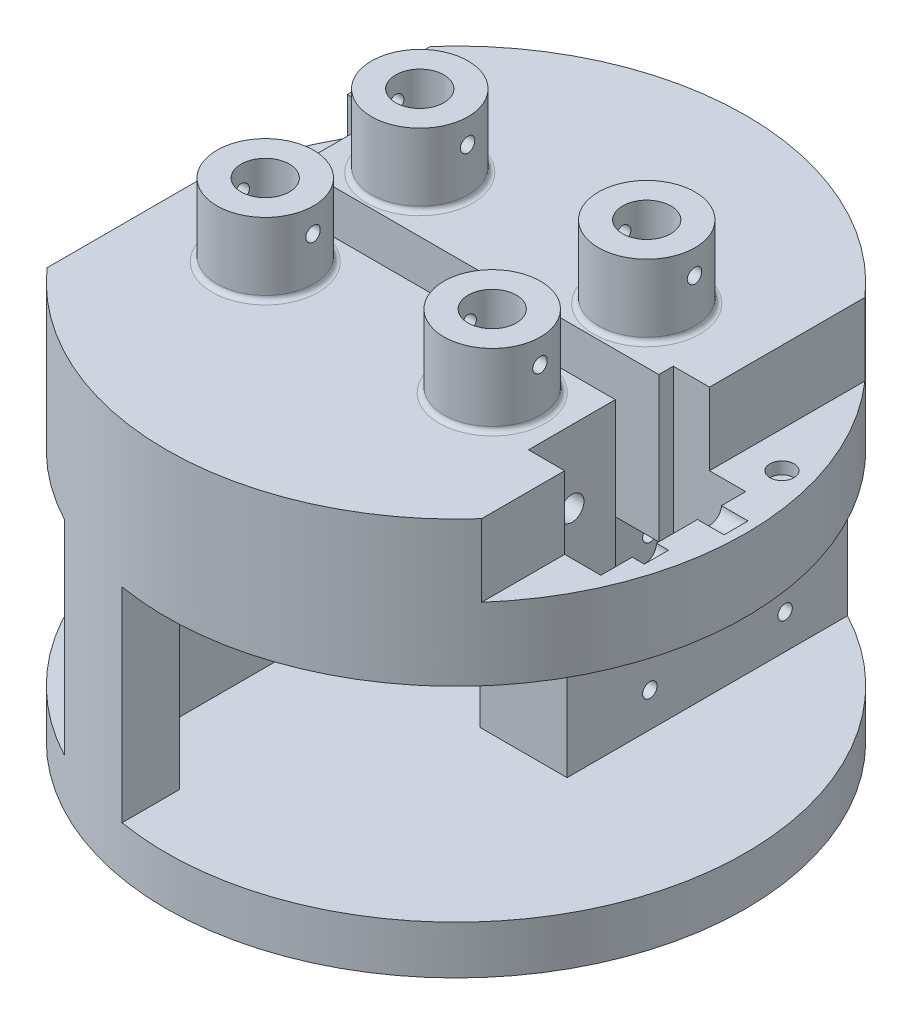
SolidWorks part; units mm, degrees
ref_plane "Front Plane" through (0, 0, 0) normal (0, 0, 1) x (1, 0, 0)
ref_plane "Top Plane" through (0, 0, 0) normal (0, 1, 0) x (1, 0, 0)
ref_plane "Right Plane" through (0, 0, 0) normal (1, 0, 0) x (0, 0, -1)
sketch "Sketch1" plane through (0, 0, 0) normal (0, 1, 0) x (1, 0, 0)
  circle A0 centre (0, 0) radius 60
  dimension "D1" = 120
extrude "Boss-Extrude1" add sketch "Sketch1" along normal blind 10
sketch "Sketch5" plane through (0, 10, 0) normal (0, 1, 0) x (1, 0, 0)
  line L0 (-73.7107, 0) -> (83.6973, 0) construction
  line L1 (0, -69.1137) -> (0, 62.4559) construction
  line L2 (0, 0) -> (20, 0) construction
  line L3 (0, 0) -> (-20, 0) construction
  line L4 (15, -47.3) -> (15, -5)
  line L5 (-15, 47.3) -> (23, 47.3)
  line L6 (-15, 47.3) -> (-15, 5)
  line L7 (-15, 5) -> (23, 5)
  line L8 (23, 47.3) -> (23, 5)
  line L9 (-15, 47.3) -> (23, 5) construction
  line L10 (-15, 5) -> (23, 47.3) construction
  line L11 (15, -47.3) -> (-23, -47.3)
  line L12 (-23, -47.3) -> (-23, -5)
  line L13 (15, -5) -> (-23, -5)
  line L15 (10, 0) -> (28, 0)
  line L16 (28, 53.066) -> (28, 0)
  line L20 (-28, -53.066) -> (-28, 0)
  line L22 (10, 59.1608) -> (10, 47.3)
  line L24 (10, 5) -> (10, 0)
  line L26 (-10, 0) -> (-10, -5)
  line L27 (-10, -47.3) -> (-10, -59.1608)
  line L28 (-10, 0) -> (-28, 0)
  line L29 (-20, 52.3) -> (28, 52.3) construction
  line L30 (-20, 52.3) -> (-20, 0) construction
  line L31 (28, 52.3) -> (28, 0) construction
  line L32 (20, -52.3) -> (20, 0) construction
  line L33 (20, -52.3) -> (-28, -52.3) construction
  line L34 (-28, -52.3) -> (-28, 0) construction
  line L35 (-20, 0) -> (28, 0) construction
  line L37 (20, 0) -> (-28, 0) construction
  line L38 (-10, 0) -> (5, 0)
  line L39 (-10, 0) -> (-10, -5)
  line L40 (-10, -5) -> (5, -5)
  line L41 (5, 0) -> (5, -5)
  line L42 (-5, 5) -> (10, 5)
  line L43 (-5, 5) -> (-5, 0)
  line L44 (-5, 0) -> (10, 0)
  line L45 (10, 5) -> (10, 0)
  circle A0 centre (0, 0) radius 60
  point P7 (4, 26.15)
  point P19 (0, 0)
  dimension "D10" = 120
  dimension "D1" = 20
  dimension "D2" = 20
  dimension "D4" = 42.3
  dimension "D5" = 5
  dimension "D6" = 5
  dimension "D7" = 38
  dimension "D11" = 20
  dimension "D12" = 10
  dimension "D9" = 10
  dimension "D13" = 5
  dimension "D8" = 5
  dimension "D3" = 2
extrude "Boss-Extrude5" add sketch "Sketch5" along normal blind 42.3 contours L7 L24 L15 L16 L22 L5 L8 | L27 L11 L12 L13 L26 L15 L20 A0 region at (-10.6184, 10, 53.2304) region at (10.6184, 10, -2.5)
sketch "Sketch6" plane through (28, 0, 0) normal (1, 0, 0) x (0, 0, -1)
  line L6 (26.15, 52.3) -> (26.15, 10) construction
  line L11 (5, 31.15) -> (47.3, 31.15) construction
  line L18 (12.15, 45.15) -> (40.15, 45.15) construction
  line L20 (5, 10) -> (47.3, 10)
  line L21 (5, 52.3) -> (5, 10)
  line L22 (47.3, 52.3) -> (5, 52.3)
  line L23 (47.3, 10) -> (47.3, 52.3)
  line L24 (5, 10) -> (47.3, 10)
  line L25 (5, 52.3) -> (5, 10)
  line L26 (47.3, 52.3) -> (5, 52.3)
  line L27 (47.3, 10) -> (47.3, 52.3)
  line L28 (12.15, 45.15) -> (12.15, 17.15) construction
  line L29 (12.15, 17.15) -> (40.15, 17.15) construction
  line L30 (40.15, 45.15) -> (40.15, 17.15) construction
  line L31 (12.15, 45.15) -> (40.15, 17.15) construction
  line L32 (12.15, 17.15) -> (40.15, 45.15) construction
  circle A4 centre (12.15, 45.15) radius 1.5
  circle A5 centre (40.15, 45.15) radius 1.5
  circle A6 centre (40.15, 17.15) radius 1.5
  circle A7 centre (12.15, 17.15) radius 1.5
  point P10 (26.15, 31.15)
  dimension "D1" = 0
  dimension "D2" = 3
  dimension "D3" = 28
  dimension "D4" = 28
extrude "Cut-Extrude1" cut sketch "Sketch6" against normal through all contours A4 | A7 | A6 | A5
pattern_circular "CirPattern1" count 2 over 360 about axis through (0, 10, 0) along (0, 1, 0) of "Cut-Extrude1"
sketch "Sketch8" plane through (0, 10, 0) normal (0, 1, 0) x (1, 0, 0)
  line L0 (10, 47.3) -> (23, 47.3) construction
  line L1 (23, 5) -> (-15, 5)
  line L2 (23, 5) -> (23, 47.3)
  line L3 (23, 47.3) -> (-15, 47.3)
  line L4 (-15, 5) -> (-15, 47.3)
  line L5 (-10, -47.3) -> (-23, -47.3) construction
  line L6 (-23, -5) -> (15, -5)
  line L7 (-23, -5) -> (-23, -47.3)
  line L8 (-23, -47.3) -> (15, -47.3)
  line L9 (15, -5) -> (15, -47.3)
  line L10 (-15, 26.15) -> (-39, 26.15) construction
  line L11 (15, -26.15) -> (39, -26.15) construction
  dimension "D1" = 38
  dimension "D2" = 38
  dimension "D3" = 24
  dimension "D4" = 24
sketch "Sketch3" plane through (0, 52.3, 0) normal (0, 1, 0) x (1, 0, 0)
  circle A11 centre (0, 0) radius 60
  dimension "D1" = 120
extrude "Boss-Extrude4" add sketch "Sketch3" along normal blind 30
sketch "Sketch4" plane through (0, 82.3, 0) normal (0, 1, 0) x (1, 0, 0)
  line L1 (-23.5, 16) -> (23.5, 16) construction
  line L2 (-23.5, 16) -> (-23.5, -16) construction
  line L3 (-23.5, -16) -> (23.5, -16) construction
  line L4 (23.5, 16) -> (23.5, -16) construction
  line L5 (-23.5, 16) -> (23.5, -16) construction
  line L6 (-23.5, -16) -> (23.5, 16) construction
  circle A0 centre (-23.5, 16) radius 5
  circle A1 centre (23.5, 16) radius 5
  circle A2 centre (23.5, -16) radius 5
  circle A3 centre (-23.5, -16) radius 5
  circle A4 centre (-23.5, 16) radius 10
  circle A5 centre (23.5, 16) radius 10
  circle A6 centre (23.5, -16) radius 10
  circle A7 centre (-23.5, -16) radius 10
  point P0 (0, 0)
  dimension "D3" = 10
  dimension "D1" = 47
  dimension "D2" = 32
  dimension "D4" = 5
extrude "Boss-Extrude6" add sketch "Sketch4" along normal blind 15
fillet "Fillet1" radius 1 4 edges at (23.5, 82.3, -6) (-23.5, 82.3, -6) (23.5, 82.3, 26) (-23.5, 82.3, 26)
sketch "Sketch7" plane through (0, 0, 0) normal (1, 0, 0) x (0, 0, -1)
  line L0 (0, 0) -> (0, 82.3) construction
  line L1 (60, 82.3) -> (-60, 82.3) construction
  line L2 (0, 82.3) -> (0, 92.3) construction
  line L3 (0, 92.3) -> (16, 92.3) construction
  line L4 (0, 92.3) -> (-16, 92.3) construction
  circle A0 centre (16, 92.3) radius 1.5
  circle A1 centre (-16, 92.3) radius 1.5
  dimension "Set screw OD" = 3
  dimension "D1" = 10
  dimension "D2" = 16
extrude "Cut-Extrude2" cut sketch "Sketch7" along normal through all both and the other way through all
sketch "Sketch9" plane through (0, 82.3, 0) normal (0, 1, 0) x (1, 0, 0)
  line L0 (-60, 0) -> (60, 0) construction
  line L1 (0, 60) -> (0, -60) construction
  line L3 (-45, 4.5) -> (45, 4.5)
  line L4 (-45, 4.5) -> (-45, -4.5)
  line L5 (-45, -4.5) -> (45, -4.5)
  line L6 (45, 4.5) -> (45, -4.5)
  line L7 (-45, 4.5) -> (45, -4.5) construction
  line L8 (-45, -4.5) -> (45, 4.5) construction
  line L9 (-52.5, 7.5) -> (-37.5, 7.5)
  line L10 (-52.5, 7.5) -> (-52.5, -7.5)
  line L11 (-52.5, -7.5) -> (-37.5, -7.5)
  line L12 (-37.5, 7.5) -> (-37.5, -7.5)
  line L13 (-52.5, 7.5) -> (-37.5, -7.5) construction
  line L14 (-52.5, -7.5) -> (-37.5, 7.5) construction
  line L15 (37.5, 7.5) -> (52.5, 7.5)
  line L16 (37.5, 7.5) -> (37.5, -7.5)
  line L17 (37.5, -7.5) -> (52.5, -7.5)
  line L18 (52.5, 7.5) -> (52.5, -7.5)
  line L19 (37.5, 7.5) -> (52.5, -7.5) construction
  line L20 (37.5, -7.5) -> (52.5, 7.5) construction
  circle A0 centre (0, 0) radius 60 construction
  point P8 (0, 0)
  point P13 (-45, 0)
  point P18 (45, 0)
  dimension "D1" = 90
  dimension "D2" = 9
  dimension "D3" = 15
  dimension "D4" = 45
extrude "Cut-Extrude6" cut sketch "Sketch9" against normal up to surface (30 mm away) contours L12 L9 L10 L11 L5 L4 L3 | L16 L3 L12 L5 | L12 L3 L4 L5 | L3 L16 L5 L6 | L18 L15 L16 L3 L6 L5 L17 region at (-46.6071, 82.3, 0) region at (-41.25, 82.3, 0) region at (0, 82.3, 0) region at (46.6071, 82.3, 0) region at (41.25, 82.3, 0) up to face at (0, 52.3, 0)
sketch "Sketch10" plane through (10, 0, 0) normal (-1, 0, 0) x (0, 0, 1)
  line L0 (-2.25, 52.3) -> (-2.25, 31.15) construction
  line L1 (-4.5, 52.3) -> (0, 52.3) construction
  circle A0 centre (-2.25, 31.15) radius 1
  dimension "Gt2 belt ID" = 2
  dimension "D1" = 21.15
sketch "Sketch11" plane through (0, 0, 0) normal (0, 0, -1) x (-1, 0, 0)
  line L1 (10, 52.3) -> (28, 52.3)
  line L2 (10, 52.3) -> (10, 10)
  line L3 (10, 10) -> (28, 10)
  line L4 (28, 52.3) -> (28, 10)
extrude "Boss-Extrude7" add sketch "Sketch11" along normal blind 5
sketch "Sketch12" plane through (-28, 0, 0) normal (-1, 0, 0) x (0, 0, 1)
  line L0 (-5, 52.3) -> (-5, 10) construction
  line L1 (-5, 52.3) -> (-5, 10)
sketch "Sketch14" plane through (0, 0, 0) normal (0, 0, 1) x (1, 0, 0)
  line L4 (10, 10) -> (28, 10)
  line L5 (28, 10) -> (28, 52.3)
  line L6 (28, 52.3) -> (10, 52.3)
  line L7 (10, 52.3) -> (10, 10)
  line L8 (10, 10) -> (28, 10)
  line L9 (28, 10) -> (28, 52.3)
  line L10 (28, 52.3) -> (10, 52.3)
  line L11 (10, 52.3) -> (10, 10)
  dimension "D1" = 0
extrude "Boss-Extrude8" add sketch "Sketch14" along normal blind 5
sketch "Sketch16" plane through (0, 82.3, 0) normal (0, 1, 0) x (1, 0, 0)
  line L0 (-37.5, -4.5) -> (-37.5, -7.5) construction
  line L1 (-52.5, 7.5) -> (-37.5, 7.5)
  line L2 (-52.5, 7.5) -> (-52.5, -7.5)
  line L3 (-52.5, -7.5) -> (-37.5, -7.5)
  line L4 (-37.5, 7.5) -> (-37.5, -7.5)
  line L5 (-52.5, -7.5) -> (-37.5, -7.5) construction
  line L7 (37.5, 7.5) -> (52.5, 7.5)
  line L8 (37.5, 7.5) -> (37.5, -7.5)
  line L9 (37.5, -7.5) -> (52.5, -7.5)
  line L10 (52.5, 7.5) -> (52.5, -7.5)
sketch "Sketch18" plane through (0, 52.3, 0) normal (0, 1, 0) x (1, 0, 0)
  line L4 (-10, -4.5) -> (-10, 4.5)
  line L5 (-10, 4.5) -> (-28, 4.5)
  line L6 (-28, 4.5) -> (-28, -4.5)
  line L7 (-28, -4.5) -> (-10, -4.5)
  line L8 (-10, -4.5) -> (-10, 4.5)
  line L9 (-10, 4.5) -> (-28, 4.5)
  line L10 (-28, 4.5) -> (-28, -4.5)
  line L11 (-28, -4.5) -> (-10, -4.5)
  line L12 (10, 4.5) -> (10, -4.5)
  line L13 (10, -4.5) -> (28, -4.5)
  line L14 (28, -4.5) -> (28, 4.5)
  line L15 (28, 4.5) -> (10, 4.5)
  line L16 (10, 4.5) -> (10, -4.5)
  line L17 (10, -4.5) -> (28, -4.5)
  line L18 (28, -4.5) -> (28, 4.5)
  line L19 (28, 4.5) -> (10, 4.5)
  dimension "D1" = 0
  dimension "D2" = 0
extrude "Boss-Extrude9" add sketch "Sketch18" along normal blind 15
sketch "Sketch19" plane through (-28, 0, 0) normal (-1, 0, 0) x (0, 0, 1)
  circle A0 centre (0, 67.5) radius 2.5
  dimension "D2" = 5
  dimension "D1" = 67.5
extrude "Cut-Extrude7" cut sketch "Sketch19" against normal blind 5 and the other way blind 30
mirror "Mirror1" about plane through (0, 0, 0) normal (1, 0, 0) of "Cut-Extrude7"
sketch "Sketch20" plane through (0, 0, 0) normal (1, 0, 0) x (0, 0, -1)
  line L0 (0, 0) -> (-50, 0) construction
  line L1 (-60, 0) -> (60, 0) construction
  circle A0 centre (-50, 0) radius 2.5
  dimension "Bearing Ball OD" = 5
  dimension "bearing ball track radius" = 50
sketch "Sketch21" plane through (0, 0, 0) normal (0, -1, 0) x (1, 0, 0)
  circle A0 centre (0, 0) radius 50
  dimension "Bearing Ball track Diameter" = 100
sweep "Cut-Sweep1" cut profiles "Sketch20" path "Sketch21"
sketch "Sketch22" plane through (0, 82.3, 0) normal (0, 1, 0) x (1, 0, 0)
  line L0 (-37.5, 7.5) -> (-37.5, -7.5) construction
  line L1 (-52.5, 7.5) -> (-37.5, 7.5)
  line L2 (-52.5, 7.5) -> (-52.5, 22.5)
  line L3 (-52.5, 22.5) -> (-37.5, 22.5)
  line L4 (-37.5, 7.5) -> (-37.5, 22.5)
  line L5 (52.5, 7.5) -> (52.5, -7.5) construction
  line L6 (37.5, -7.5) -> (52.5, -7.5)
  line L7 (37.5, -7.5) -> (37.5, -22.5)
  line L8 (37.5, -22.5) -> (52.5, -22.5)
  line L9 (52.5, -7.5) -> (52.5, -22.5)
  dimension "D1" = 15
  dimension "D2" = 15
extrude "Cut-Extrude8" cut sketch "Sketch22" against normal up to next
sketch "Sketch24" plane through (-37.5, 0, 0) normal (-1, 0, 0) x (0, 0, 1)
  line L0 (-13.5, 82.3) -> (-13.5, 52.3) construction
  line L1 (-22.5, 67.3) -> (-4.5, 67.3) construction
  line L4 (-4.5, 52.3) -> (-4.5, 82.3)
  line L5 (-4.5, 82.3) -> (-22.5, 82.3)
  line L6 (-22.5, 82.3) -> (-22.5, 52.3)
  line L7 (-22.5, 52.3) -> (-4.5, 52.3)
  line L8 (-4.5, 52.3) -> (-4.5, 82.3) construction
  line L9 (-4.5, 82.3) -> (-22.5, 82.3) construction
  line L10 (-22.5, 82.3) -> (-22.5, 52.3) construction
  line L11 (-22.5, 52.3) -> (-4.5, 52.3) construction
  circle A0 centre (-13.5, 67.3) radius 2.5
  dimension "D2" = 5
  dimension "D1" = 0
extrude "Cut-Extrude9" cut sketch "Sketch24" along normal blind 17.5 and the other way blind 5
sketch "Sketch25" plane through (37.5, 0, 0) normal (1, 0, 0) x (0, 0, -1)
  line L0 (-13.5, 82.3) -> (-13.5, 52.3) construction
  line L1 (-22.5, 67.3) -> (-4.5, 67.3) construction
  line L4 (-22.5, 52.3) -> (-4.5, 52.3)
  line L5 (-4.5, 52.3) -> (-4.5, 82.3)
  line L6 (-4.5, 82.3) -> (-22.5, 82.3)
  line L7 (-22.5, 82.3) -> (-22.5, 52.3)
  line L8 (-22.5, 52.3) -> (-4.5, 52.3) construction
  line L9 (-4.5, 52.3) -> (-4.5, 82.3) construction
  line L10 (-4.5, 82.3) -> (-22.5, 82.3) construction
  line L11 (-22.5, 82.3) -> (-22.5, 52.3) construction
  circle A0 centre (-13.5, 67.3) radius 2.5
  dimension "D2" = 5
  dimension "D1" = 0
extrude "Cut-Extrude10" cut sketch "Sketch25" along normal blind 17.5 and the other way blind 5
sketch "Sketch26" plane through (0, 82.3, 0) normal (0, 1, 0) x (1, 0, 0)
  line L0 (45, 7.5) -> (45, 39.6863)
  line L1 (-52.5, 22.5) -> (-45, 22.5)
  line L2 (-52.5, 22.5) -> (-52.5, -7.5)
  line L3 (-52.5, -7.5) -> (-45, -7.5)
  line L5 (45, 7.5) -> (52.5, 7.5)
  line L7 (45, -22.5) -> (52.5, -22.5)
  line L8 (52.5, 7.5) -> (52.5, -22.5)
  line L9 (45, -22.5) -> (45, -39.6863)
  line L10 (-45, -7.5) -> (-45, -39.6863)
  line L11 (-45, 22.5) -> (-45, 39.6863)
  circle A0 centre (0, 0) radius 60 construction
  arc A1 (-45, 39.6863) -> (-45, -39.6863) centre (0, 0) ccw
  arc A2 (45, -39.6863) -> (45, 39.6863) centre (0, 0) ccw
extrude "Cut-Extrude11" cut sketch "Sketch26" against normal blind 15
sketch "Sketch27" plane through (0, 67.3, 0) normal (0, 1, 0) x (1, 0, 0)
  line L0 (52.5, 7.5) -> (52.5, 15) construction
  line L1 (-52.5, -7.5) -> (-52.5, -15) construction
  circle A0 centre (-52.5, -15) radius 2.5
  circle A1 centre (52.5, 15) radius 2.5
  dimension "D2" = 5
  dimension "D1" = 7.5
extrude "Cut-Extrude12" cut sketch "Sketch27" against normal blind 2.5
